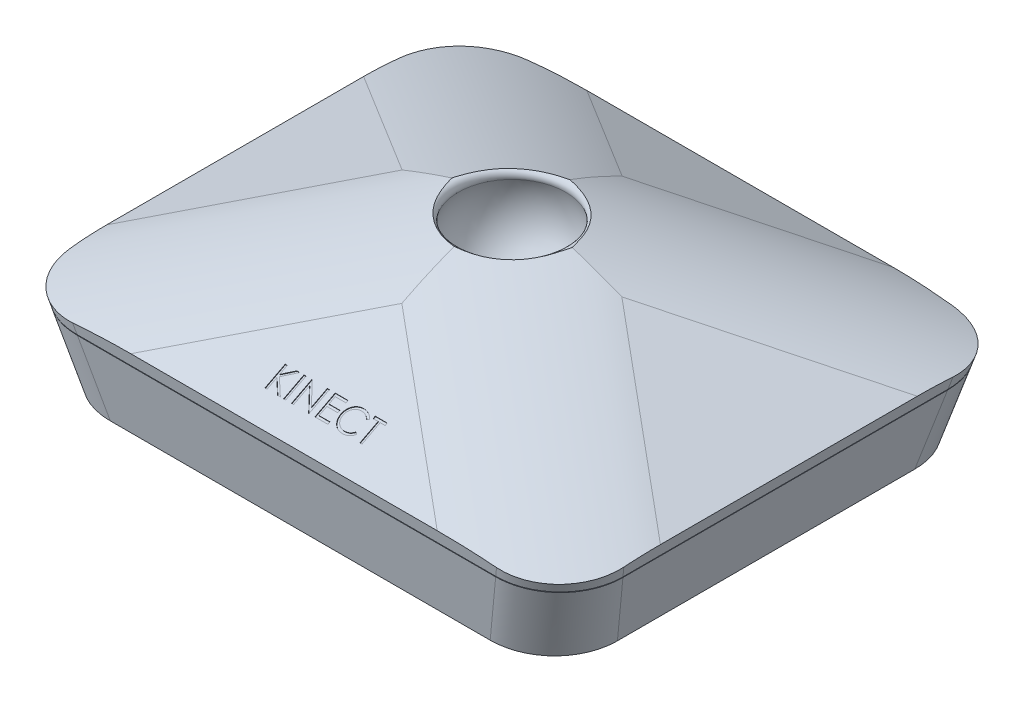
SolidWorks part; units mm, degrees
ref_plane "Front Plane" through (0, 0, 0) normal (0, 0, 1) x (1, 0, 0)
ref_plane "Top Plane" through (0, 0, 0) normal (0, 1, 0) x (1, 0, 0)
ref_plane "Right Plane" through (0, 0, 0) normal (1, 0, 0) x (0, 0, -1)
sketch "Sketch1" plane through (0, 0, 0) normal (0, 1, 0) x (1, 0, 0)
  line L1 (-42.5, 35) -> (42.5, 35)
  line L2 (-42.5, 35) -> (-42.5, -35)
  line L3 (-42.5, -35) -> (42.5, -35)
  line L4 (42.5, 35) -> (42.5, -35)
  line L5 (-42.5, 35) -> (42.5, -35) construction
  line L6 (-42.5, -35) -> (42.5, 35) construction
  point P0 (0, 0)
extrude "Boss-Extrude1" add sketch "Sketch1" along normal blind 26
sketch "Sketch2" plane through (0, 0, 35) normal (0, 0, 1) x (1, 0, 0)
  line L0 (-39, 0) -> (-42.5, 0)
  line L1 (-42.5, 0) -> (42.5, 0) construction
  line L2 (39, 0) -> (42.5, 0)
  line L4 (42.5, 26) -> (42.5, 0) construction
  line L5 (-42.5, 26) -> (-42.5, 0) construction
  line L6 (-42.5, 13) -> (-39, 0)
  line L7 (-42.5, 0) -> (-42.5, 13)
  line L8 (42.5, 13) -> (39, 0)
  line L9 (42.5, 0) -> (42.5, 13)
extrude "Cut-Extrude1" cut sketch "Sketch2" against normal through all
sketch "Sketch3" plane through (0, 0, 35) normal (0, 0, 1) x (1, 0, 0)
  line L0 (-10, 26) -> (-42.5, 13)
  line L1 (-42.5, 26) -> (42.5, 26) construction
  line L3 (-42.5, 13) -> (-42.5, 26)
  line L4 (-42.5, 26) -> (-10, 26)
  line L5 (10, 26) -> (42.5, 13)
  line L6 (42.5, 13) -> (42.5, 26)
  line L7 (42.5, 26) -> (10, 26)
extrude "Cut-Extrude2" cut sketch "Sketch3" against normal through all
sketch "Sketch4" plane through (0, 0, 0) normal (1, 0, 0) x (0, 0, -1)
  line L0 (32.5, 0) -> (35, 13)
  line L1 (35, 0) -> (-35, 0) construction
  line L3 (35, 13) -> (35, 0)
  line L4 (35, 0) -> (32.5, 0)
  line L5 (-32.5, 0) -> (-35, 13)
  line L6 (-35, 13) -> (-35, 0)
  line L7 (-35, 0) -> (-32.5, 0)
extrude "Cut-Extrude3" cut sketch "Sketch4" against normal through all and the other way through all
sketch "Sketch5" plane through (0, 0, 0) normal (1, 0, 0) x (0, 0, -1)
  line L0 (10, 26) -> (35, 13)
  line L1 (35, 26) -> (-35, 26) construction
  line L3 (35, 13) -> (35, 26)
  line L4 (35, 26) -> (10, 26)
  line L5 (-10, 26) -> (-35, 13)
  line L6 (-35, 13) -> (-35, 26)
  line L7 (-35, 26) -> (-10, 26)
extrude "Cut-Extrude4" cut sketch "Sketch5" against normal through all and the other way through all
sketch "Sketch7" plane through (0, 26, 0) normal (0, 1, 0) x (1, 0, 0)
  line L1 (-2.5, 2.5) -> (2.5, 2.5)
  line L2 (-2.5, 2.5) -> (-2.5, -2.5)
  line L3 (-2.5, -2.5) -> (2.5, -2.5)
  line L4 (2.5, 2.5) -> (2.5, -2.5)
  line L5 (-2.5, 2.5) -> (2.5, -2.5) construction
  line L6 (-2.5, -2.5) -> (2.5, 2.5) construction
  point P0 (0, 0)
extrude "Cut-Extrude5" cut sketch "Sketch7" against normal blind 5
sketch "Sketch8" plane through (0, 21, 0) normal (0, 1, 0) x (1, 0, 0)
  line L0 (-17.1014, 0) -> (19.9364, 0) construction
  line L1 (-9, 0) -> (9, 0)
  arc A0 (9, 0) -> (-9, 0) centre (0, 0) ccw
revolve "Cut-Revolve3" cut sketch "Sketch8" angle 360 about L0
fillet "Fillet1" radius 40 4 edges at (26.25, 19.5, -22.5) (-26.25, 19.5, -22.5) (-26.25, 19.5, 22.5) (26.25, 19.5, 22.5)
fillet "Fillet2" radius 10 4 edges at (-40.5078, 5.6003, -33.577) (40.5078, 5.6003, -33.577) (40.5078, 5.6003, 33.577) (-40.5078, 5.6003, 33.577)
fillet "Fillet3" radius 1 1 edges at (0, 26, 7.4833)
sketch "Sketch9" plane through (0, 24.5592, 12.7708) normal (0, 0.8872, 0.4614) x (1, 0, 0)
  text T0 "KINECT"
extrude "Cut-Extrude6" cut sketch "Sketch9" against normal blind 0.1
sketch "Sketch10" plane through (0, 0, 0) normal (0, -1, 0) x (1, 0, 0)
  line L0 (-29.1523, 31.8032) -> (29.1523, 31.8032)
  line L1 (-38.1307, 22.8167) -> (-38.1307, -22.8167)
  line L2 (29.1523, -31.8032) -> (-29.1523, -31.8032)
  line L3 (38.1307, -22.8167) -> (38.1307, 22.8167)
  arc A0 (-29.1523, 31.8032) -> (-38.1307, 22.8167) centre (-28.6439, 22.3168) ccw
  arc A1 (-38.1307, -22.8167) -> (-29.1523, -31.8032) centre (-28.6439, -22.3168) ccw
  arc A2 (29.1523, -31.8032) -> (38.1307, -22.8167) centre (28.6439, -22.3168) ccw
  arc A3 (38.1307, 22.8167) -> (29.1523, 31.8032) centre (28.6439, 22.3168) ccw
  dimension "D1" = 19
  dimension "D2" = 19
  dimension "D3" = 19
  dimension "D4" = 19
extrude "Boss-Extrude2" add sketch "Sketch10" along normal blind 0.5
sketch "Sketch11" plane through (0, 0, 0) normal (0, 0, 1) x (1, 0, 0)
  line L3 (-47.5, 11.05) -> (47.5, 11.05)
  line L4 (-47.5, 11.05) -> (-47.5, 10.95)
  line L5 (-47.5, 10.95) -> (47.5, 10.95)
  line L6 (47.5, 11.05) -> (47.5, 10.95)
  line L7 (-47.5, 11.05) -> (47.5, 10.95) construction
  line L8 (-47.5, 10.95) -> (47.5, 11.05) construction
extrude "Cut-Extrude7" cut sketch "Sketch11" against normal blind 10 from offset 35
mirror "Mirror1" about plane through (0, 0, 0) normal (0, 0, 1) of "Cut-Extrude7"
sketch "Sketch12" plane through (0, 0, 0) normal (1, 0, 0) x (0, 0, -1)
  line L3 (25, 10.95) -> (-25, 10.95)
  line L4 (25, 10.95) -> (25, 11.05)
  line L5 (25, 11.05) -> (-25, 11.05)
  line L6 (-25, 10.95) -> (-25, 11.05)
  line L7 (25, 10.95) -> (-25, 11.05) construction
  line L8 (25, 11.05) -> (-25, 10.95) construction
extrude "Cut-Extrude8" cut sketch "Sketch12" against normal blind 1 from offset 42.5
mirror "Mirror2" about plane through (0, 0, 0) normal (1, 0, 0) of "Cut-Extrude8"
sketch "Sketch13" plane through (0, -0.5, 0) normal (0, -1, 0) x (1, 0, 0)
  line L4 (-36.25, 3.75) -> (-31.25, 3.75)
  line L5 (-36.25, 3.75) -> (-36.25, -3.75)
  line L6 (-36.25, -3.75) -> (-31.25, -3.75)
  line L7 (-31.25, 3.75) -> (-31.25, -3.75)
  line L8 (-36.25, 3.75) -> (-31.25, -3.75) construction
  line L9 (-36.25, -3.75) -> (-31.25, 3.75) construction
  circle A0 centre (-33.75, 10) radius 2.5
  circle A1 centre (-33.75, -10) radius 2.5
extrude "Cut-Extrude9" cut sketch "Sketch13" against normal blind 4
mirror "Mirror3" about plane through (0, 0, 0) normal (1, 0, 0) of "Cut-Extrude9"
sketch "Sketch14" plane through (0, -0.5, 0) normal (0, -1, 0) x (1, 0, 0)
  line L0 (-30.75, -10) -> (-30.75, 10)
  line L1 (-38.1307, 13.75) -> (-33.2781, 12.9626)
  line L2 (-38.1307, 22.8167) -> (-38.1307, -22.8167) construction
  line L3 (-38.1307, 13.75) -> (-38.1307, -13.75)
  line L4 (-38.1307, -13.75) -> (-33.2695, -12.9612)
  arc A0 (-30.75, 10) -> (-33.2781, 12.9626) centre (-33.75, 10) ccw
  arc A1 (-33.2695, -12.9612) -> (-30.75, -10) centre (-33.75, -10) ccw
extrude "Cut-Extrude10" cut sketch "Sketch14" against normal blind 0.5
mirror "Mirror4" about plane through (0, 0, 0) normal (1, 0, 0) of "Cut-Extrude10"
